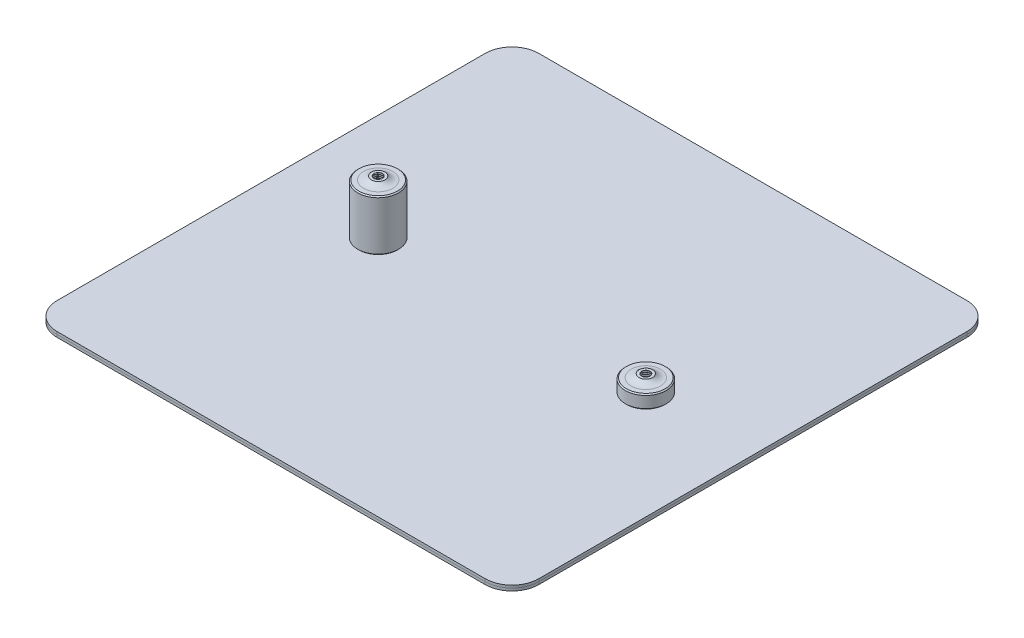
SolidWorks part; units mm, degrees
ref_plane "Alzado" through (0, 0, 0) normal (0, 0, 1) x (1, 0, 0)
ref_plane "Planta" through (0, 0, 0) normal (0, 1, 0) x (1, 0, 0)
ref_plane "Vista lateral" through (0, 0, 0) normal (1, 0, 0) x (0, 0, -1)
sketch "Croquis1" plane through (0, 0, 0) normal (0, 1, 0) x (1, 0, 0)
  line L0 (125, 0) -> (-125, 0) construction
  line L1 (-200, 225) -> (200, 225)
  line L2 (-225, 200) -> (-225, -200)
  line L3 (-200, -225) -> (200, -225)
  line L4 (225, 200) -> (225, -200)
  line L5 (-225, 225) -> (225, -225) construction
  line L6 (-225, -225) -> (225, 225) construction
  line L7 (-125, 0) -> (-353.8098, -100.7277) construction
  line L8 (-353.8098, -100.7277) -> (0, -225) construction
  line L9 (0, -225) -> (353.8098, -100.7277) construction
  line L10 (353.8098, -100.7277) -> (125, 0) construction
  line L11 (0, 0) -> (0, 47.3377) construction
  arc A0 (-225, -200) -> (-200, -225) centre (-200, -200) ccw
  arc A1 (200, -225) -> (225, -200) centre (200, -200) ccw
  arc A2 (200, 225) -> (225, 200) centre (200, 200) cw
  arc A3 (-200, 225) -> (-225, 200) centre (-200, 200) ccw
  circle A4 centre (-125, 0) radius 4.9022
  circle A5 centre (125, 0) radius 4.9022
  point P0 (0, 0)
  point P8 (0, 0)
  point P15 (0, -229.9955)
  point P16 (0, -225)
  dimension "D5" = 25
  dimension "D6" = 9.8044
  dimension "D1" = 450
  dimension "D2" = 450
  dimension "D3" = 250
  dimension "D4" = 375
extrude "Saliente-Extruir1" add sketch "Croquis1" along normal blind 2.4
mirror "Simetría1" about plane through (-200, 2.4, 200) normal (0, 1, 0) of bodies 101
sketch "Croquis2" plane through (0, 4.8, 0) normal (0, 1, 0) x (1, 0, 0)
  circle A0 centre (-125, 0) radius 19.05
  circle A1 centre (-125, 0) radius 3.9687
  dimension "D1" = 38.1
  dimension "D2" = 7.9375
extrude "Saliente-Extruir2" add sketch "Croquis2" along normal blind 47.625 separate body
sketch "Croquis3" plane through (0, 52.425, 0) normal (0, 1, 0) x (1, 0, 0)
  circle A0 centre (-125, 0) radius 6.35
  circle A1 centre (-125, 0) radius 3.9687 construction
  circle A2 centre (-125, 0) radius 3.9687
  dimension "D1" = 12.7
extrude "Saliente-Extruir3" add sketch "Croquis3" along normal blind 3.175
fillet "Redondeo1" radius 10 1 edges at (-125, 52.425, 6.35)
thread "Rosca1" pitch 1.5875 profile "Perfil de rosca1" start angle 0, offset 0, length 0, pitch 1.5875, diameter 7.9375
ref_plane "Plano1" through (-128.9688, 55.6, 0) normal (0, 0, 1) x (-1, 0, 0)
sketch "Perfil de rosca1" plane through (-128.9688, 55.6, 0) normal (0, 0, 1) x (-1, 0, 0)
  line L0 (0, 0) -> (0, 1.5875) construction
  line L1 (0, 0) -> (0.8593, 0.4961)
  line L2 (0.8593, 0.4961) -> (0.8593, 0.6945)
  line L3 (0.8593, 0.6945) -> (0, 1.1906)
  line L4 (0.8593, 0.5953) -> (0, 0.5953) construction
  line L11 (0, 0) -> (0, 1.1906)
  point P2 (0, 0)
  dimension "Pitch" = 1.5875
  dimension "Profile_Angle" = 60
  dimension "Profile_Land" = 0.1984
  dimension "Profile_Height" = 0.8593
sketch "Croquis6" plane through (0, 4.8, 0) normal (0, 1, 0) x (1, 0, 0)
  circle A0 centre (125, 0) radius 19.05
  circle A1 centre (-125, 0) radius 19.05 construction
  circle A2 centre (125, 0) radius 3.9687
  circle A3 centre (-125, 0) radius 3.9687 construction
extrude "Saliente-Extruir4" add sketch "Croquis6" along normal blind 12.7 separate body
sketch "Croquis7" plane through (0, 17.5, 0) normal (0, 1, 0) x (1, 0, 0)
  circle A0 centre (125, 0) radius 6.35
  circle A1 centre (125, 0) radius 3.9687 construction
  circle A2 centre (125, 0) radius 3.9687
  dimension "D1" = 12.7
extrude "Saliente-Extruir5" add sketch "Croquis7" along normal blind 3.175
fillet "Redondeo2" radius 10 1 edges at (125, 17.5, 6.35)
thread "Rosca2" pitch 1.5875 profile "Perfil de rosca2" start angle 0, offset 0, length 0, pitch 1.5875, diameter 7.9375
ref_plane "Plano2" through (121.0313, 20.675, 0) normal (0, 0, 1) x (-1, 0, 0)
sketch "Perfil de rosca2" plane through (121.0313, 20.675, 0) normal (0, 0, 1) x (-1, 0, 0)
  line L0 (0, 0) -> (0, 1.5875) construction
  line L1 (0, 0) -> (0.8593, 0.4961)
  line L2 (0.8593, 0.4961) -> (0.8593, 0.6945)
  line L3 (0.8593, 0.6945) -> (0, 1.1906)
  line L4 (0.8593, 0.5953) -> (0, 0.5953) construction
  line L11 (0, 0) -> (0, 1.1906)
  point P2 (0, 0)
  dimension "Pitch" = 1.5875
  dimension "Profile_Angle" = 60
  dimension "Profile_Land" = 0.1984
  dimension "Profile_Height" = 0.8593
chamfer "Chaflán1" distance 1 angle 45 2 edges at (-125, 4.8, 19.05) (-125, 52.425, 19.05)
chamfer "Chaflán2" distance 1 angle 45 2 edges at (125, 4.8, 19.05) (125, 17.5, 19.05)
